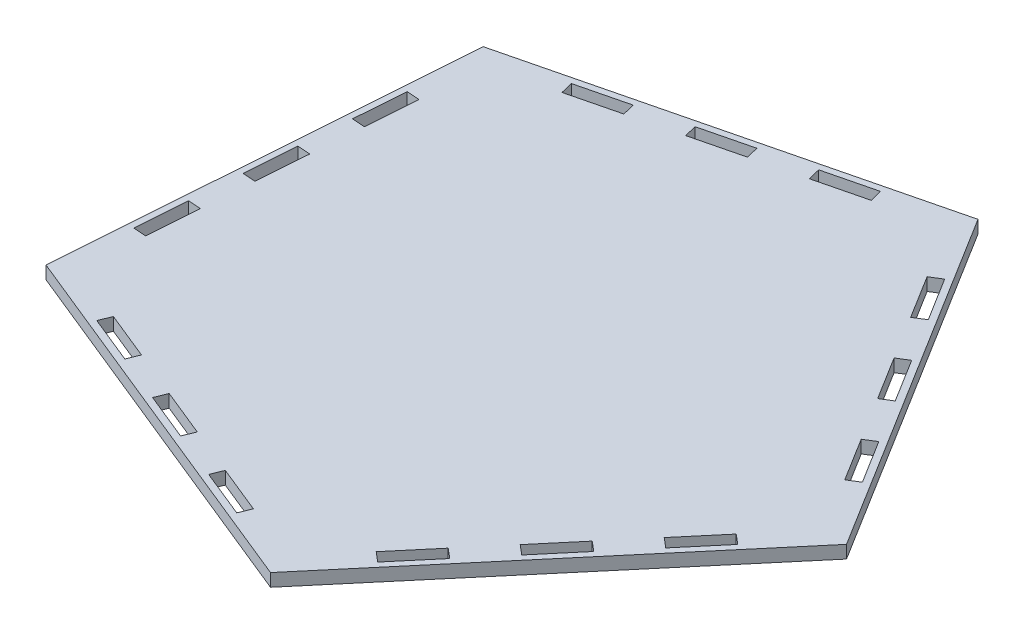
SolidWorks part; units mm, degrees
ref_plane "Front Plane" through (0, 0, 0) normal (0, 0, 1) x (1, 0, 0)
ref_plane "Top Plane" through (0, 0, 0) normal (0, 1, 0) x (1, 0, 0)
ref_plane "Right Plane" through (0, 0, 0) normal (1, 0, 0) x (0, 0, -1)
sketch "Sketch1" plane through (0, 0, 0) normal (0, 1, 0) x (1, 0, 0)
  line L1 (-472.7621, -38.6016) -> (-579.997, 133.9989)
  line L2 (-579.997, 133.9989) -> (-777.2872, 85.3489)
  line L3 (-777.2872, 85.3489) -> (-791.9844, -117.3188)
  line L4 (-791.9844, -117.3188) -> (-603.7775, -193.9245)
  line L5 (-603.7775, -193.9245) -> (-472.7621, -38.6016)
  circle A0 centre (-645.1616, -26.0994) radius 139.8404 construction
  dimension "D1" = 203.2
extrude "Boss-Extrude1" add sketch "Sketch1" along normal blind 6.35
sketch "Sketch2" plane through (0, 6.35, 0) normal (0, 1, 0) x (1, 0, 0)
  line L1 (-659.0013, -161.163) -> (-635.4754, -170.7387)
  line L2 (-659.0013, -161.163) -> (-661.3952, -167.0445)
  line L3 (-661.3952, -167.0445) -> (-637.8693, -176.6202)
  line L4 (-635.4754, -170.7387) -> (-637.8693, -176.6202)
  line L5 (-706.053, -142.0116) -> (-682.5271, -151.5873)
  line L6 (-791.9844, -117.3188) -> (-603.7775, -193.9245) construction
  line L7 (-753.0539, -122.7353) -> (-729.528, -132.311)
  line L8 (-753.0539, -122.7353) -> (-755.4478, -128.6168)
  line L9 (-755.4478, -128.6168) -> (-731.9219, -138.1925)
  line L10 (-729.528, -132.311) -> (-731.9219, -138.1925)
  line L11 (-706.053, -142.0116) -> (-708.4469, -147.8931)
  line L12 (-708.4469, -147.8931) -> (-684.921, -157.4688)
  line L13 (-682.5271, -151.5873) -> (-684.921, -157.4688)
  dimension "D1" = 3.175
  dimension "D2" = 6.35
  dimension "D3" = 25.4
  dimension "D4" = 38.1
  dimension "D5" = 25.4
  dimension "D6" = 6.35
  dimension "D7" = 38.1
  dimension "D8" = 3.175
  dimension "D9" = 6.35
  dimension "D10" = 25.4
  dimension "D11" = 25.4
extrude "Cut-Extrude1" cut sketch "Sketch2" against normal through all
sketch "Sketch4" plane through (0, 6.35, 0) normal (0, 1, 0) x (1, 0, 0)
  line L0 (-603.7775, -193.9245) -> (-472.7621, -38.6016) construction
  line L1 (-570.116, -139.2447) -> (-565.2621, -143.339)
  line L2 (-570.116, -139.2447) -> (-586.4929, -158.6601)
  line L3 (-586.4929, -158.6601) -> (-581.639, -162.7543)
  line L4 (-565.2621, -143.339) -> (-581.639, -162.7543)
  line L6 (-520.9852, -80.9987) -> (-516.1313, -85.0929)
  line L7 (-520.9852, -80.9987) -> (-504.6082, -61.5833)
  line L8 (-504.6082, -61.5833) -> (-499.7544, -65.6775)
  line L9 (-516.1313, -85.0929) -> (-499.7544, -65.6775)
  line L10 (-548.8852, -123.9236) -> (-532.5083, -104.5082)
  line L11 (-548.8852, -123.9236) -> (-553.739, -119.8294)
  line L12 (-553.739, -119.8294) -> (-537.3621, -100.414)
  line L13 (-532.5083, -104.5082) -> (-537.3621, -100.414)
  dimension "D1" = 6.35
  dimension "D2" = 25.4
  dimension "D3" = 3.175
  dimension "D4" = 38.1
  dimension "D5" = 3.175
  dimension "D6" = 6.35
  dimension "D7" = 25.4
  dimension "D8" = 38.1
  dimension "D9" = 6.35
  dimension "D10" = 25.4
  dimension "D11" = 3.175
  dimension "D12" = 25.4
extrude "Cut-Extrude2" cut sketch "Sketch4" against normal through all
sketch "Sketch5" plane through (0, 6.35, 0) normal (0, 1, 0) x (1, 0, 0)
  line L0 (-777.2872, 85.3489) -> (-791.9844, -117.3188) construction
  line L1 (-777.8914, -54.6741) -> (-784.2248, -54.2148)
  line L2 (-777.8914, -54.6741) -> (-779.7286, -80.0076)
  line L3 (-779.7286, -80.0076) -> (-786.0619, -79.5483)
  line L4 (-784.2248, -54.2148) -> (-786.0619, -79.5483)
  line L6 (-774.2171, -4.0071) -> (-780.5505, -3.5479)
  line L7 (-774.2171, -4.0071) -> (-776.0543, -29.3406)
  line L8 (-776.0543, -29.3406) -> (-782.3876, -28.8813)
  line L9 (-780.5505, -3.5479) -> (-782.3876, -28.8813)
  line L10 (-776.8762, 47.1191) -> (-770.5428, 46.6598)
  line L11 (-776.8762, 47.1191) -> (-778.7133, 21.7856)
  line L12 (-778.7133, 21.7856) -> (-772.38, 21.3263)
  line L13 (-770.5428, 46.6598) -> (-772.38, 21.3263)
  dimension "D1" = 6.35
  dimension "D2" = 25.4
  dimension "D3" = 3.175
  dimension "D4" = 38.1
  dimension "D5" = 25.4
  dimension "D6" = 6.35
  dimension "D7" = 3.175
  dimension "D8" = 25.4
  dimension "D9" = 6.35
  dimension "D10" = 25.4
  dimension "D11" = 3.175
  dimension "D12" = 38.1
extrude "Cut-Extrude3" cut sketch "Sketch5" against normal through all
sketch "Sketch6" plane through (0, 6.35, 0) normal (0, 1, 0) x (1, 0, 0)
  line L0 (-472.7621, -38.6016) -> (-579.997, 133.9989) construction
  line L1 (-508.9699, 13.6605) -> (-495.5655, -7.9146)
  line L2 (-508.9699, 13.6605) -> (-514.3636, 10.3094)
  line L3 (-514.3636, 10.3094) -> (-500.9593, -11.2656)
  line L4 (-495.5655, -7.9146) -> (-500.9593, -11.2656)
  line L6 (-522.3742, 35.2356) -> (-527.768, 31.8845)
  line L7 (-522.3742, 35.2356) -> (-535.7786, 56.8106)
  line L8 (-535.7786, 56.8106) -> (-541.1724, 53.4595)
  line L9 (-527.768, 31.8845) -> (-541.1724, 53.4595)
  line L10 (-549.1398, 78.4125) -> (-554.5336, 75.0614)
  line L11 (-549.1398, 78.4125) -> (-562.5442, 99.9876)
  line L12 (-562.5442, 99.9876) -> (-567.9379, 96.6365)
  line L13 (-554.5336, 75.0614) -> (-567.9379, 96.6365)
  dimension "D1" = 6.35
  dimension "D2" = 25.4
  dimension "D3" = 3.175
  dimension "D4" = 38.1
  dimension "D5" = 6.35
  dimension "D6" = 25.4
  dimension "D7" = 3.175
  dimension "D8" = 25.4
  dimension "D9" = 25.4
  dimension "D10" = 6.35
  dimension "D11" = 3.1242
  dimension "D12" = 38.1
extrude "Cut-Extrude4" cut sketch "Sketch6" against normal through all
sketch "Sketch7" plane through (0, 6.35, 0) normal (0, 1, 0) x (1, 0, 0)
  line L0 (-579.997, 133.9989) -> (-777.2872, 85.3489) construction
  line L1 (-614.7084, 115.629) -> (-639.3697, 109.5478)
  line L2 (-614.7084, 115.629) -> (-616.2287, 121.7944)
  line L3 (-616.2287, 121.7944) -> (-640.89, 115.7131)
  line L4 (-639.3697, 109.5478) -> (-640.89, 115.7131)
  line L6 (-665.5513, 109.6319) -> (-690.2125, 103.5506)
  line L7 (-665.5513, 109.6319) -> (-664.031, 103.4666)
  line L8 (-664.031, 103.4666) -> (-688.6922, 97.3853)
  line L9 (-690.2125, 103.5506) -> (-688.6922, 97.3853)
  line L10 (-714.8738, 97.4694) -> (-739.5351, 91.3882)
  line L11 (-714.8738, 97.4694) -> (-713.3535, 91.3041)
  line L12 (-713.3535, 91.3041) -> (-738.0148, 85.2228)
  line L13 (-739.5351, 91.3882) -> (-738.0148, 85.2228)
  point P7 (-615.4686, 118.7117)
  dimension "D1" = 25.4
  dimension "D2" = 6.35
  dimension "D3" = 3.175
  dimension "D4" = 38.1
  dimension "D5" = 6.35
  dimension "D6" = 25.4
  dimension "D7" = 3.175
  dimension "D8" = 25.4
  dimension "D9" = 25.4
  dimension "D10" = 6.35
  dimension "D11" = 3.175
  dimension "D12" = 25.4
extrude "Cut-Extrude5" cut sketch "Sketch7" against normal through all
